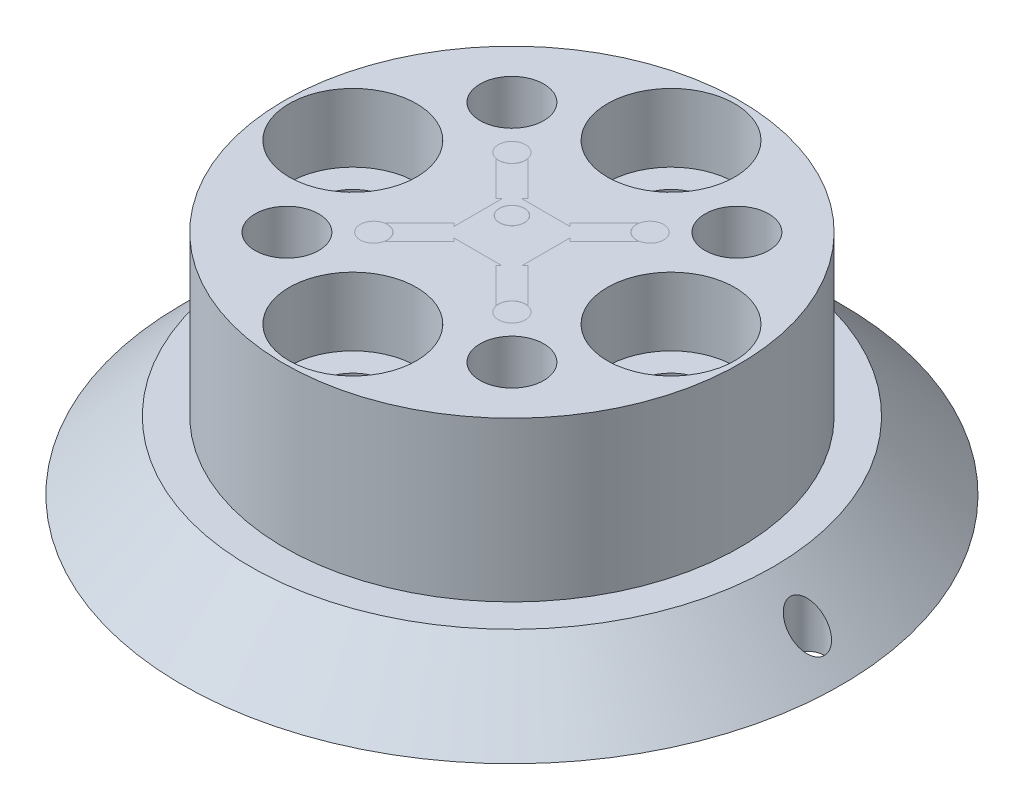
SolidWorks part; units mm, degrees
other "graphite_1"
other "blue_1"
other "white_4"
other "white_2"
other "white_5"
other "white"
other "white_3"
ref_plane "Front Plane" through (0, 0, 0) normal (0, 0, 1) x (1, 0, 0)
ref_plane "Top Plane" through (0, 0, 0) normal (0, 1, 0) x (1, 0, 0)
ref_plane "Right Plane" through (0, 0, 0) normal (1, 0, 0) x (0, 0, -1)
sketch "Sketch1" plane through (0, 0, 0) normal (0, 0, 1) x (1, 0, 0)
  line L0 (14.5, 0) -> (11.5, 3)
  line L1 (11.5, 3) -> (10.025, 3)
  line L2 (10.025, 3) -> (10.025, 10)
  line L3 (10.025, 10) -> (0, 10)
  line L4 (14.5, 0) -> (0, 0)
  line L5 (0, 10) -> (0, 0) construction
  line L6 (0, 10) -> (0, 0)
  dimension "D1" = 20.05
  dimension "D2" = 23
  dimension "D3" = 3
  dimension "D4" = 3
  dimension "D5" = 7
revolve "Revolve1" add sketch "Sketch1" angle 360 about L5
sketch "Sketch2" plane through (0, 10, 0) normal (0, 1, 0) x (1, 0, 0)
  line L0 (0, 0) -> (0, 7) construction
  circle A0 centre (0, 7) radius 1.4
  circle A1 centre (4.9497, 4.9497) radius 1.4
  circle A2 centre (7, 0) radius 1.4
  circle A3 centre (4.9497, -4.9497) radius 1.4
  circle A4 centre (0, -7) radius 1.4
  circle A5 centre (-4.9497, -4.9497) radius 1.4
  circle A6 centre (-7, 0) radius 1.4
  circle A7 centre (-4.9497, 4.9497) radius 1.4
  point P13 (0, 0)
  dimension "D1" = 2.8
  dimension "D2" = 7
  dimension "D3" = 8
extrude "Cut-Extrude1" cut sketch "Sketch2" against normal through all
hole_wizard "CBORE for M5 Hex Head Bolt1" positions "3DSketch1" profile "Sketch3" counterbore size "M5" standard "ANSI Metric" end condition through all
sketch3d "3DSketch1"
  line L0 (0, 0, -7) -> (0, 10, -7) construction
  line L1 (-7, 0, 0) -> (-7, 10, 0) construction
  line L2 (0, 0, 7) -> (0, 10, 7) construction
  line L3 (7, 0, 0) -> (7, 10, 0) construction
  point P0 (0, 10, -7)
  point P4 (-7, 10, 0)
  point P8 (0, 10, 7)
  point P12 (7, 10, 0)
sketch "Sketch3" plane through (0, 10, -7) normal (1, 0, 0) x (0, 0, 1)
  line L0 (0, 0) -> (0, 10)
  line L1 (0, 10) -> (1.6, 10)
  line L3 (1.6, 10) -> (1.6, 3)
  line L4 (1.6, 3) -> (2.8, 3)
  line L5 (2.8, 3) -> (2.8, 0)
  line L7 (2.8, 0) -> (0, 0)
  line L11 (0, -6.35) -> (0, 107.95) construction
  dimension "Thru Hole Dia." = 3.2
  dimension "Thru Hole Depth" = 10
  dimension "C'Bore Dia." = 5.6
  dimension "C'Bore Depth" = 3
sketch "Sketch4" plane through (0, 0, 0) normal (0, 1, 0) x (1, 0, 0)
  line L0 (0, 0) -> (13, 0) construction
  circle A0 centre (13, 0) radius 0.75
  dimension "D1" = 1.5
  dimension "D2" = 13
extrude "Cut-Extrude3" cut sketch "Sketch4" along normal through all
sketch "GL_end_blue" plane through (0, 0, 0) normal (0, 1, 0) x (1, 0, 0)
  line L0 (-0.9263, -1.6263) -> (-2.4462, -3.1463)
  line L1 (-2.4462, -3.1463) -> (-2.4355, -3.0404)
  line L2 (-2.4355, -3.0404) -> (-2.4616, -2.8649)
  line L3 (-2.4616, -2.8649) -> (-2.5374, -2.7045)
  line L4 (-2.5374, -2.7045) -> (-2.6128, -2.6126)
  line L5 (-2.6128, -2.6126) -> (-2.7552, -2.507)
  line L6 (-2.7552, -2.507) -> (-2.865, -2.4615)
  line L7 (-2.865, -2.4615) -> (-3.0404, -2.4355)
  line L8 (-3.0404, -2.4355) -> (-3.1463, -2.4462)
  line L9 (-3.1463, -2.4462) -> (-1.6263, -0.9263)
  line L10 (-1.6263, -0.9263) -> (-1.495, -1.0577)
  line L11 (-1.495, -1.0577) -> (-1.495, 1.0577)
  line L12 (-1.495, 1.0577) -> (-1.6263, 0.9263)
  line L13 (-1.6263, 0.9263) -> (-3.1463, 2.4462)
  line L14 (-3.1463, 2.4462) -> (-3.0404, 2.4355)
  line L15 (-3.0404, 2.4355) -> (-2.8649, 2.4616)
  line L16 (-2.8649, 2.4616) -> (-2.7045, 2.5374)
  line L17 (-2.7045, 2.5374) -> (-2.6126, 2.6128)
  line L18 (-2.6126, 2.6128) -> (-2.507, 2.7552)
  line L19 (-2.507, 2.7552) -> (-2.4615, 2.865)
  line L20 (-2.4615, 2.865) -> (-2.4355, 3.0404)
  line L21 (-2.4355, 3.0404) -> (-2.4462, 3.1463)
  line L22 (-2.4462, 3.1463) -> (-0.9263, 1.6263)
  line L23 (-0.9263, 1.6263) -> (-1.0577, 1.495)
  line L24 (-1.0577, 1.495) -> (1.0577, 1.495)
  line L25 (1.0577, 1.495) -> (0.9263, 1.6263)
  line L26 (0.9263, 1.6263) -> (2.4462, 3.1463)
  line L27 (2.4462, 3.1463) -> (2.4355, 3.0404)
  line L28 (2.4355, 3.0404) -> (2.4616, 2.8649)
  line L29 (2.4616, 2.8649) -> (2.5374, 2.7045)
  line L30 (2.5374, 2.7045) -> (2.6127, 2.6127)
  line L31 (2.6127, 2.6127) -> (2.7045, 2.5374)
  line L32 (2.7045, 2.5374) -> (2.8649, 2.4616)
  line L33 (2.8649, 2.4616) -> (3.0404, 2.4355)
  line L34 (3.0404, 2.4355) -> (3.1463, 2.4462)
  line L35 (3.1463, 2.4462) -> (1.6263, 0.9263)
  line L36 (1.6263, 0.9263) -> (1.495, 1.0577)
  line L37 (1.495, 1.0577) -> (1.495, -1.0577)
  line L38 (1.495, -1.0577) -> (1.6263, -0.9263)
  line L39 (1.6263, -0.9263) -> (3.1463, -2.4462)
  line L40 (3.1463, -2.4462) -> (3.0404, -2.4355)
  line L41 (3.0404, -2.4355) -> (2.865, -2.4615)
  line L42 (2.865, -2.4615) -> (2.7552, -2.507)
  line L43 (2.7552, -2.507) -> (2.6128, -2.6126)
  line L44 (2.6128, -2.6126) -> (2.5374, -2.7045)
  line L45 (2.5374, -2.7045) -> (2.4616, -2.8649)
  line L46 (2.4616, -2.8649) -> (2.4355, -3.0404)
  line L47 (2.4355, -3.0404) -> (2.4462, -3.1463)
  line L48 (2.4462, -3.1463) -> (0.9263, -1.6263)
  line L49 (0.9263, -1.6263) -> (1.0577, -1.495)
  line L50 (1.0577, -1.495) -> (-1.0577, -1.495)
  line L51 (-1.0577, -1.495) -> (-0.9263, -1.6263)
  line L52 (-0.084, 0.582) -> (-0.084, 0.6908)
  line L53 (-0.084, 0.6908) -> (-0.1053, 0.7975)
  line L54 (-0.1053, 0.7975) -> (-0.1469, 0.898)
  line L55 (-0.1469, 0.898) -> (-0.2074, 0.9885)
  line L56 (-0.2074, 0.9885) -> (-0.2843, 1.0654)
  line L57 (-0.2843, 1.0654) -> (-0.3748, 1.1259)
  line L58 (-0.3748, 1.1259) -> (-0.4753, 1.1675)
  line L59 (-0.4753, 1.1675) -> (-0.582, 1.1887)
  line L60 (-0.582, 1.1887) -> (-0.6908, 1.1887)
  line L61 (-0.6908, 1.1887) -> (-0.7975, 1.1675)
  line L62 (-0.7975, 1.1675) -> (-0.898, 1.1259)
  line L63 (-0.898, 1.1259) -> (-0.9885, 1.0654)
  line L64 (-0.9885, 1.0654) -> (-1.0654, 0.9885)
  line L65 (-1.0654, 0.9885) -> (-1.1259, 0.898)
  line L66 (-1.1259, 0.898) -> (-1.1675, 0.7975)
  line L67 (-1.1675, 0.7975) -> (-1.1887, 0.6908)
  line L68 (-1.1887, 0.6908) -> (-1.1887, 0.582)
  line L69 (-1.1887, 0.582) -> (-1.1675, 0.4753)
  line L70 (-1.1675, 0.4753) -> (-1.1259, 0.3748)
  line L71 (-1.1259, 0.3748) -> (-1.0654, 0.2843)
  line L72 (-1.0654, 0.2843) -> (-0.9885, 0.2074)
  line L73 (-0.9885, 0.2074) -> (-0.898, 0.1469)
  line L74 (-0.898, 0.1469) -> (-0.7975, 0.1053)
  line L75 (-0.7975, 0.1053) -> (-0.6908, 0.084)
  line L76 (-0.6908, 0.084) -> (-0.582, 0.084)
  line L77 (-0.582, 0.084) -> (-0.4753, 0.1053)
  line L78 (-0.4753, 0.1053) -> (-0.3748, 0.1469)
  line L79 (-0.3748, 0.1469) -> (-0.2843, 0.2074)
  line L80 (-0.2843, 0.2074) -> (-0.2074, 0.2843)
  line L81 (-0.2074, 0.2843) -> (-0.1469, 0.3748)
  line L82 (-0.1469, 0.3748) -> (-0.1053, 0.4753)
  line L83 (-0.1053, 0.4753) -> (-0.084, 0.582)
extrude "GL_end_blue_cut" cut sketch "GL_end_blue" along normal blind 1.1 from offset 9.4
extrude "GL_end_blue_inlay" add sketch "GL_end_blue<2>" along normal blind 0.6 from offset 9.4 separate body
sketch "GL_end_blue<2>" plane through (0, 0, 0) normal (0, 1, 0) x (1, 0, 0) same geometry as "GL_end_blue"
sketch "GL_end_white" plane through (0, 0, 0) normal (0, 1, 0) x (1, 0, 0)
  line L0 (3.5353, -3.3711) -> (3.4613, -3.4613)
  line L1 (3.4613, -3.4613) -> (3.3711, -3.5353)
  line L2 (3.3711, -3.5353) -> (3.2682, -3.5902)
  line L3 (3.2682, -3.5902) -> (3.1566, -3.6241)
  line L4 (3.1566, -3.6241) -> (3.0406, -3.6355)
  line L5 (3.0406, -3.6355) -> (2.9245, -3.6241)
  line L6 (2.9245, -3.6241) -> (2.8129, -3.5902)
  line L7 (2.8129, -3.5902) -> (2.71, -3.5353)
  line L8 (2.71, -3.5353) -> (2.6198, -3.4613)
  line L9 (2.6198, -3.4613) -> (2.5459, -3.3711)
  line L10 (2.5459, -3.3711) -> (2.4909, -3.2682)
  line L11 (2.4909, -3.2682) -> (2.457, -3.1566)
  line L12 (2.457, -3.1566) -> (2.4456, -3.0406)
  line L13 (2.4456, -3.0406) -> (2.457, -2.9245)
  line L14 (2.457, -2.9245) -> (2.4909, -2.8129)
  line L15 (2.4909, -2.8129) -> (2.5459, -2.71)
  line L16 (2.5459, -2.71) -> (2.6198, -2.6198)
  line L17 (2.6198, -2.6198) -> (2.71, -2.5459)
  line L18 (2.71, -2.5459) -> (2.8129, -2.4909)
  line L19 (2.8129, -2.4909) -> (2.9245, -2.457)
  line L20 (2.9245, -2.457) -> (3.0406, -2.4456)
  line L21 (3.0406, -2.4456) -> (3.1566, -2.457)
  line L22 (3.1566, -2.457) -> (3.2682, -2.4909)
  line L23 (3.2682, -2.4909) -> (3.3711, -2.5459)
  line L24 (3.3711, -2.5459) -> (3.4613, -2.6198)
  line L25 (3.4613, -2.6198) -> (3.5353, -2.71)
  line L26 (3.5353, -2.71) -> (3.5902, -2.8129)
  line L27 (3.5902, -2.8129) -> (3.6241, -2.9245)
  line L28 (3.6241, -2.9245) -> (3.6355, -3.0406)
  line L29 (3.6355, -3.0406) -> (3.6241, -3.1566)
  line L30 (3.6241, -3.1566) -> (3.5902, -3.2682)
  line L31 (3.5902, -3.2682) -> (3.5353, -3.3711)
  line L32 (-2.5459, -3.3711) -> (-2.6198, -3.4613)
  line L33 (-2.6198, -3.4613) -> (-2.71, -3.5353)
  line L34 (-2.71, -3.5353) -> (-2.8129, -3.5902)
  line L35 (-2.8129, -3.5902) -> (-2.9245, -3.6241)
  line L36 (-2.9245, -3.6241) -> (-3.0406, -3.6355)
  line L37 (-3.0406, -3.6355) -> (-3.1566, -3.6241)
  line L38 (-3.1566, -3.6241) -> (-3.2682, -3.5902)
  line L39 (-3.2682, -3.5902) -> (-3.3711, -3.5353)
  line L40 (-3.3711, -3.5353) -> (-3.4613, -3.4613)
  line L41 (-3.4613, -3.4613) -> (-3.5353, -3.3711)
  line L42 (-3.5353, -3.3711) -> (-3.5902, -3.2682)
  line L43 (-3.5902, -3.2682) -> (-3.6241, -3.1566)
  line L44 (-3.6241, -3.1566) -> (-3.6355, -3.0406)
  line L45 (-3.6355, -3.0406) -> (-3.6241, -2.9245)
  line L46 (-3.6241, -2.9245) -> (-3.5902, -2.8129)
  line L47 (-3.5902, -2.8129) -> (-3.5353, -2.71)
  line L48 (-3.5353, -2.71) -> (-3.4613, -2.6198)
  line L49 (-3.4613, -2.6198) -> (-3.3711, -2.5459)
  line L50 (-3.3711, -2.5459) -> (-3.2682, -2.4909)
  line L51 (-3.2682, -2.4909) -> (-3.1566, -2.457)
  line L52 (-3.1566, -2.457) -> (-3.0406, -2.4456)
  line L53 (-3.0406, -2.4456) -> (-2.9245, -2.457)
  line L54 (-2.9245, -2.457) -> (-2.8129, -2.4909)
  line L55 (-2.8129, -2.4909) -> (-2.71, -2.5459)
  line L56 (-2.71, -2.5459) -> (-2.6198, -2.6198)
  line L57 (-2.6198, -2.6198) -> (-2.5459, -2.71)
  line L58 (-2.5459, -2.71) -> (-2.4909, -2.8129)
  line L59 (-2.4909, -2.8129) -> (-2.457, -2.9245)
  line L60 (-2.457, -2.9245) -> (-2.4456, -3.0406)
  line L61 (-2.4456, -3.0406) -> (-2.457, -3.1566)
  line L62 (-2.457, -3.1566) -> (-2.4909, -3.2682)
  line L63 (-2.4909, -3.2682) -> (-2.5459, -3.3711)
  line L64 (-0.1833, 0.3336) -> (-0.251, 0.251)
  line L65 (-0.251, 0.251) -> (-0.3336, 0.1833)
  line L66 (-0.3336, 0.1833) -> (-0.4278, 0.1329)
  line L67 (-0.4278, 0.1329) -> (-0.5301, 0.1019)
  line L68 (-0.5301, 0.1019) -> (-0.6364, 0.0914)
  line L69 (-0.6364, 0.0914) -> (-0.7427, 0.1019)
  line L70 (-0.7427, 0.1019) -> (-0.8449, 0.1329)
  line L71 (-0.8449, 0.1329) -> (-0.9392, 0.1833)
  line L72 (-0.9392, 0.1833) -> (-1.0218, 0.251)
  line L73 (-1.0218, 0.251) -> (-1.0895, 0.3336)
  line L74 (-1.0895, 0.3336) -> (-1.1399, 0.4278)
  line L75 (-1.1399, 0.4278) -> (-1.1709, 0.5301)
  line L76 (-1.1709, 0.5301) -> (-1.1814, 0.6364)
  line L77 (-1.1814, 0.6364) -> (-1.1709, 0.7427)
  line L78 (-1.1709, 0.7427) -> (-1.1399, 0.8449)
  line L79 (-1.1399, 0.8449) -> (-1.0895, 0.9392)
  line L80 (-1.0895, 0.9392) -> (-1.0218, 1.0218)
  line L81 (-1.0218, 1.0218) -> (-0.9392, 1.0895)
  line L82 (-0.9392, 1.0895) -> (-0.8449, 1.1399)
  line L83 (-0.8449, 1.1399) -> (-0.7427, 1.1709)
  line L84 (-0.7427, 1.1709) -> (-0.6364, 1.1814)
  line L85 (-0.6364, 1.1814) -> (-0.5301, 1.1709)
  line L86 (-0.5301, 1.1709) -> (-0.4278, 1.1399)
  line L87 (-0.4278, 1.1399) -> (-0.3336, 1.0895)
  line L88 (-0.3336, 1.0895) -> (-0.251, 1.0218)
  line L89 (-0.251, 1.0218) -> (-0.1833, 0.9392)
  line L90 (-0.1833, 0.9392) -> (-0.1329, 0.8449)
  line L91 (-0.1329, 0.8449) -> (-0.1019, 0.7427)
  line L92 (-0.1019, 0.7427) -> (-0.0914, 0.6364)
  line L93 (-0.0914, 0.6364) -> (-0.1019, 0.5301)
  line L94 (-0.1019, 0.5301) -> (-0.1329, 0.4278)
  line L95 (-0.1329, 0.4278) -> (-0.1833, 0.3336)
  line L96 (-2.6198, 2.6198) -> (-2.71, 2.5459)
  line L97 (-2.71, 2.5459) -> (-2.8129, 2.4909)
  line L98 (-2.8129, 2.4909) -> (-2.9245, 2.457)
  line L99 (-2.9245, 2.457) -> (-3.0406, 2.4456)
  line L100 (-3.0406, 2.4456) -> (-3.1566, 2.457)
  line L101 (-3.1566, 2.457) -> (-3.2682, 2.4909)
  line L102 (-3.2682, 2.4909) -> (-3.3711, 2.5459)
  line L103 (-3.3711, 2.5459) -> (-3.4613, 2.6198)
  line L104 (-3.4613, 2.6198) -> (-3.5353, 2.71)
  line L105 (-3.5353, 2.71) -> (-3.5902, 2.8129)
  line L106 (-3.5902, 2.8129) -> (-3.6241, 2.9245)
  line L107 (-3.6241, 2.9245) -> (-3.6355, 3.0406)
  line L108 (-3.6355, 3.0406) -> (-3.6241, 3.1566)
  line L109 (-3.6241, 3.1566) -> (-3.5902, 3.2682)
  line L110 (-3.5902, 3.2682) -> (-3.5353, 3.3711)
  line L111 (-3.5353, 3.3711) -> (-3.4613, 3.4613)
  line L112 (-3.4613, 3.4613) -> (-3.3711, 3.5353)
  line L113 (-3.3711, 3.5353) -> (-3.2682, 3.5902)
  line L114 (-3.2682, 3.5902) -> (-3.1566, 3.6241)
  line L115 (-3.1566, 3.6241) -> (-3.0406, 3.6355)
  line L116 (-3.0406, 3.6355) -> (-2.9245, 3.6241)
  line L117 (-2.9245, 3.6241) -> (-2.8129, 3.5902)
  line L118 (-2.8129, 3.5902) -> (-2.71, 3.5353)
  line L119 (-2.71, 3.5353) -> (-2.6198, 3.4613)
  line L120 (-2.6198, 3.4613) -> (-2.5459, 3.3711)
  line L121 (-2.5459, 3.3711) -> (-2.4909, 3.2682)
  line L122 (-2.4909, 3.2682) -> (-2.457, 3.1566)
  line L123 (-2.457, 3.1566) -> (-2.4456, 3.0406)
  line L124 (-2.4456, 3.0406) -> (-2.457, 2.9245)
  line L125 (-2.457, 2.9245) -> (-2.4909, 2.8129)
  line L126 (-2.4909, 2.8129) -> (-2.5459, 2.71)
  line L127 (-2.5459, 2.71) -> (-2.6198, 2.6198)
  line L128 (3.4613, 2.6198) -> (3.3711, 2.5459)
  line L129 (3.3711, 2.5459) -> (3.2682, 2.4909)
  line L130 (3.2682, 2.4909) -> (3.1566, 2.457)
  line L131 (3.1566, 2.457) -> (3.0406, 2.4456)
  line L132 (3.0406, 2.4456) -> (2.9245, 2.457)
  line L133 (2.9245, 2.457) -> (2.8129, 2.4909)
  line L134 (2.8129, 2.4909) -> (2.71, 2.5459)
  line L135 (2.71, 2.5459) -> (2.6198, 2.6198)
  line L136 (2.6198, 2.6198) -> (2.5459, 2.71)
  line L137 (2.5459, 2.71) -> (2.4909, 2.8129)
  line L138 (2.4909, 2.8129) -> (2.457, 2.9245)
  line L139 (2.457, 2.9245) -> (2.4456, 3.0406)
  line L140 (2.4456, 3.0406) -> (2.457, 3.1566)
  line L141 (2.457, 3.1566) -> (2.4909, 3.2682)
  line L142 (2.4909, 3.2682) -> (2.5459, 3.3711)
  line L143 (2.5459, 3.3711) -> (2.6198, 3.4613)
  line L144 (2.6198, 3.4613) -> (2.71, 3.5353)
  line L145 (2.71, 3.5353) -> (2.8129, 3.5902)
  line L146 (2.8129, 3.5902) -> (2.9245, 3.6241)
  line L147 (2.9245, 3.6241) -> (3.0406, 3.6355)
  line L148 (3.0406, 3.6355) -> (3.1566, 3.6241)
  line L149 (3.1566, 3.6241) -> (3.2682, 3.5902)
  line L150 (3.2682, 3.5902) -> (3.3711, 3.5353)
  line L151 (3.3711, 3.5353) -> (3.4613, 3.4613)
  line L152 (3.4613, 3.4613) -> (3.5353, 3.3711)
  line L153 (3.5353, 3.3711) -> (3.5902, 3.2682)
  line L154 (3.5902, 3.2682) -> (3.6241, 3.1566)
  line L155 (3.6241, 3.1566) -> (3.6355, 3.0406)
  line L156 (3.6355, 3.0406) -> (3.6241, 2.9245)
  line L157 (3.6241, 2.9245) -> (3.5902, 2.8129)
  line L158 (3.5902, 2.8129) -> (3.5353, 2.71)
  line L159 (3.5353, 2.71) -> (3.4613, 2.6198)
extrude "GL_end_white_cut" cut sketch "GL_end_white" along normal blind 1.1 from offset 9.4
extrude "GL_end_white_inlay" add sketch "GL_end_white<2>" along normal blind 0.6 from offset 9.4 separate body
sketch "GL_end_white<2>" plane through (0, 0, 0) normal (0, 1, 0) x (1, 0, 0) same geometry as "GL_end_white"
